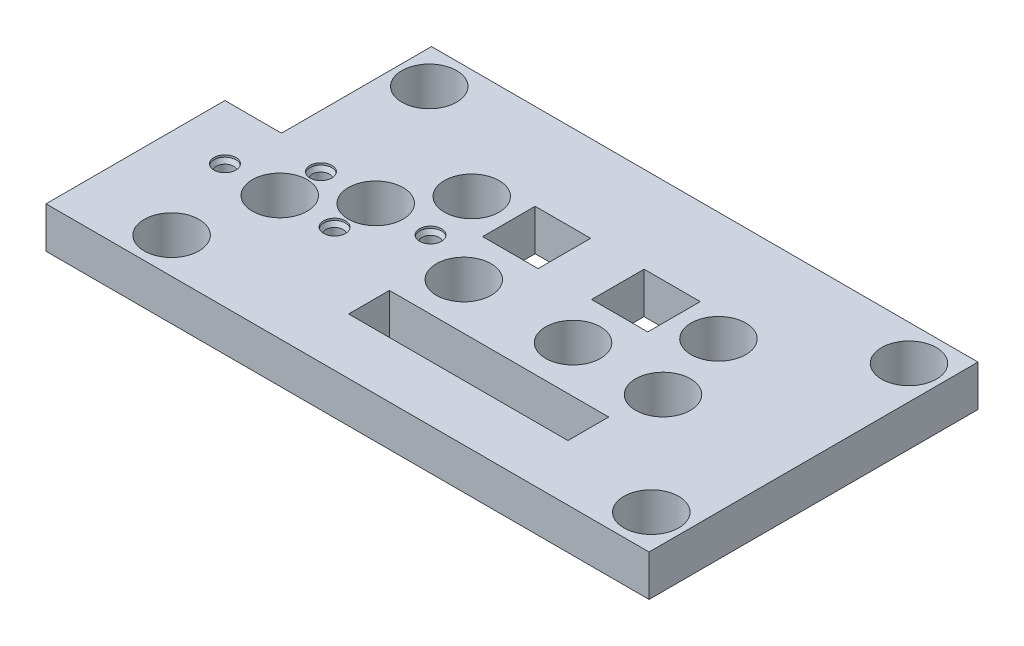
SolidWorks part; units mm, degrees
material "Plain Carbon Steel"
ref_plane "Front Plane" through (0, 0, 0) normal (0, 0, 1) x (1, 0, 0)
ref_plane "Top Plane" through (0, 0, 0) normal (0, 1, 0) x (1, 0, 0)
ref_plane "Right Plane" through (0, 0, 0) normal (1, 0, 0) x (0, 0, -1)
sketch "Sketch1" plane through (0, 0, 0) normal (0, 1, 0) x (1, 0, 0)
  line L1 (-110, -60) -> (110, -60)
  line L2 (-110, -60) -> (-110, 60)
  line L3 (-110, 60) -> (110, 60)
  line L4 (110, -60) -> (110, 60)
  line L5 (-110, -60) -> (110, 60) construction
  line L6 (-110, 60) -> (110, -60) construction
  point P0 (0, 0)
  dimension "D1" = 120
  dimension "D2" = 220
extrude "Boss-Extrude1" add sketch "Sketch1" against normal blind 15
sketch "Sketch2" plane through (0, 0, 0) normal (0, 1, 0) x (1, 0, 0)
  line L1 (-110, 60) -> (-89.3675, 60)
  line L2 (-110, 60) -> (-110, 5.27)
  line L3 (-110, 5.27) -> (-89.3675, 5.27)
  line L4 (-89.3675, 60) -> (-89.3675, 5.27)
  line L5 (-90, -14.72) -> (-89.3675, 5.27) construction
  line L10 (-70, 0.28) -> (-89.3675, 5.27) construction
  circle A0 centre (-70, 0.28) radius 3.1 construction
  circle A1 centre (-90, -14.72) radius 3.1 construction
  dimension "D1" = 20
extrude "Cut-Extrude1" cut sketch "Sketch2" against normal up to next
sketch "Sketch3" plane through (0, 0, 0) normal (0, 1, 0) x (1, 0, 0)
  line L0 (-20, 27.5) -> (-20, 9.28) construction
  line L1 (-20, 9.28) -> (0.25, 9.28) construction
  line L2 (0.25, 9.28) -> (0.25, 27.5) construction
  line L3 (19.75, 27.5) -> (19.75, 9.28) construction
  line L4 (19.75, 9.28) -> (40.25, 9.28) construction
  line L5 (40.25, 9.28) -> (40.25, 27.5) construction
  line L6 (-20, 28.44) -> (-20, 9.28)
  line L7 (-20, 9.28) -> (0.25, 9.28)
  line L8 (0.25, 9.28) -> (0.25, 28.44)
  line L9 (19.75, 28.44) -> (19.75, 9.28)
  line L10 (19.75, 9.28) -> (40.25, 9.28)
  line L11 (40.25, 9.28) -> (40.25, 28.44)
  line L12 (-20, 28.44) -> (0.25, 28.44)
  line L14 (19.75, 28.44) -> (40.25, 28.44)
  line L15 (0.31, 28.5) -> (-20.06, 28.5) construction
  dimension "D1" = 0.06
extrude "Cut-Extrude2" cut sketch "Sketch3" against normal up to next
sketch "Sketch4" plane through (0, 0, 0) normal (0, 1, 0) x (1, 0, 0)
  line L0 (-20.06, -39.66) -> (60.06, -39.66) construction
  line L1 (60, -24.72) -> (-20, -24.72)
  line L2 (60, -24.72) -> (60, -39.6)
  line L3 (60, -39.6) -> (-20, -39.6)
  line L4 (-20, -24.72) -> (-20, -39.6)
  dimension "D1" = 80
  dimension "D2" = 0.06
  dimension "D3" = 14.88
extrude "Cut-Extrude3" cut sketch "Sketch4" against normal up to next
hole_wizard "Ø6.2 (6.2) Diameter Hole1" positions "Sketch7" profile "Sketch6" hole size "Ø6.2" standard "ISO" end condition through all
sketch "Sketch7" plane through (0, 0, 0) normal (0, 1, 0) x (1, 0, 0)
  point P0 (-30, 0.28)
  point P3 (-50, -14.72)
  point P6 (-70, 0.28)
  point P9 (-90, -14.72)
sketch "Sketch6" plane through (-30, 0, -0.28) normal (1, 0, 0) x (0, 0, 1)
  line L0 (0, 0) -> (0, 15)
  line L1 (0, 15) -> (3.1, 15)
  line L2 (3.1, 15) -> (3.1, 0)
  line L5 (3.1, 0) -> (0, 0)
  line L11 (0, -6.35) -> (0, 107.95) construction
  dimension "Thru Hole Dia." = 6.2
  dimension "Thru Hole Depth" = 15
sketch "Sketch8" plane through (0, 0, 0) normal (0, 1, 0) x (1, 0, 0)
  circle A0 centre (-90, -14.72) radius 4
  circle A1 centre (-70, 0.28) radius 4
  circle A2 centre (-50, -14.72) radius 4
  circle A3 centre (-30, 0.28) radius 4
  dimension "D1" = 8
extrude "Cut-Extrude4" cut sketch "Sketch8" against normal blind 0.5
chamfer "Chamfer1" distance 1.8 angle 30 4 edges at (-90, -0.5, 17.82) (-30, -0.5, 2.82) (-50, -0.5, 17.82) (-70, -0.5, 2.82) first distance on face at (-90, -15, 17.82) first distance on face at (-30, -15, 2.82) first distance on face at (-50, -15, 17.82) first distance on face at (-70, -15, 2.82)
sketch "Sketch9" plane through (0, 0, 0) normal (0, 1, 0) x (1, 0, 0)
  circle A0 centre (-77.1837, -47) radius 10 construction
  circle A1 centre (97.8163, -47) radius 10 construction
  circle A2 centre (62.8163, -7.72) radius 10 construction
  circle A3 centre (30, -7.72) radius 10 construction
  circle A4 centre (-9.875, -7.72) radius 10 construction
  circle A5 centre (-70, -14.72) radius 10 construction
  circle A6 centre (-50, 0.28) radius 10 construction
  circle A7 centre (55.3163, 20) radius 10 construction
  circle A8 centre (97.8163, 47) radius 10 construction
  circle A12 centre (-34.6837, 20) radius 10 construction
  circle A13 centre (-77.1837, 47) radius 10 construction
  circle A14 centre (-77.1837, -47) radius 10
  circle A15 centre (97.8163, -47) radius 10
  circle A16 centre (62.8163, -7.72) radius 10
  circle A17 centre (30, -7.72) radius 10
  circle A18 centre (-9.875, -7.72) radius 10
  circle A19 centre (-70, -14.72) radius 10
  circle A20 centre (-50, 0.28) radius 10
  circle A21 centre (55.3163, 20) radius 10
  circle A22 centre (97.8163, 47) radius 10
  circle A26 centre (-34.6837, 20) radius 10
  circle A27 centre (-77.1837, 47) radius 10
extrude "Cut-Extrude5" cut sketch "Sketch9" against normal up to next
